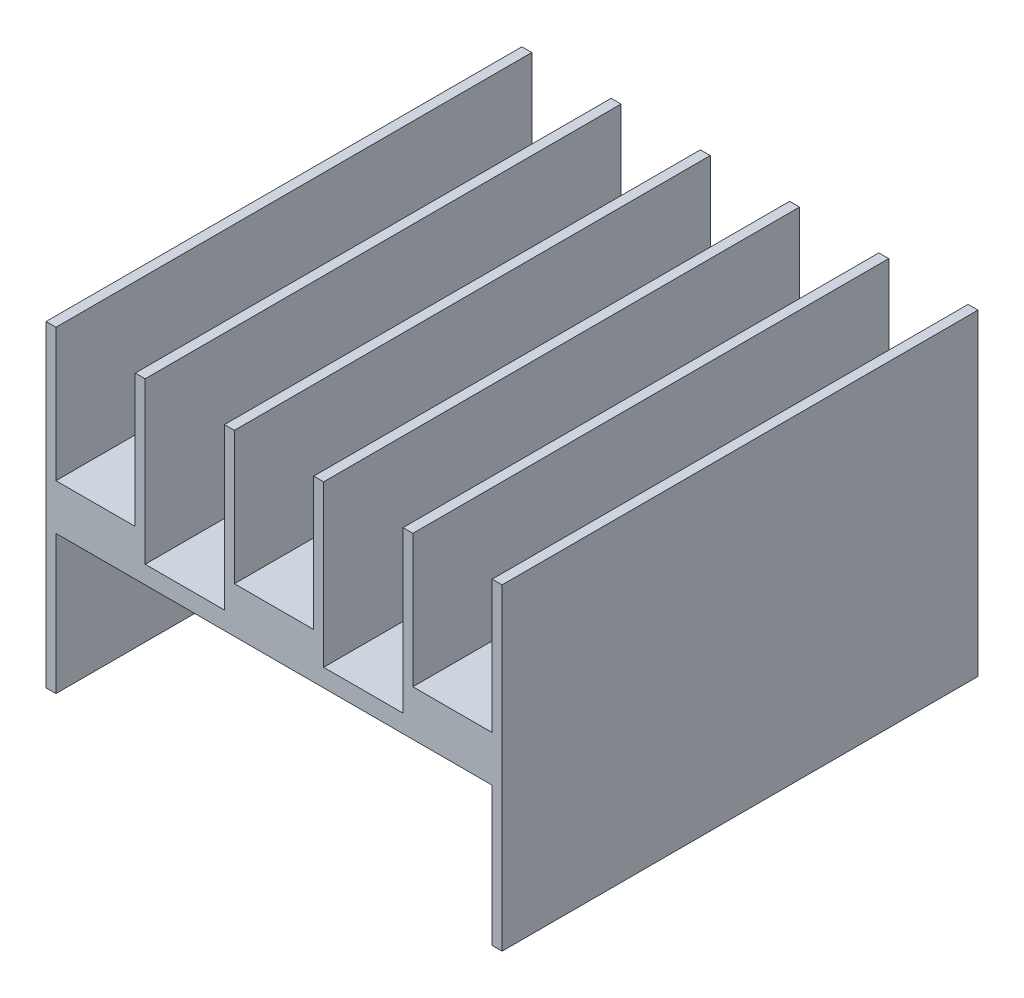
SolidWorks part; units mm, degrees
ref_plane "Front Plane" through (0, 0, 0) normal (0, 0, 1) x (1, 0, 0)
ref_plane "Top Plane" through (0, 0, 0) normal (0, 1, 0) x (1, 0, 0)
ref_plane "Right Plane" through (0, 0, 0) normal (1, 0, 0) x (0, 0, -1)
sketch "Sketch1" plane through (0, 0, 0) normal (0, 0, 1) x (1, 0, 0)
  line L0 (-11, 8) -> (-11, 1.3)
  line L5 (-11.5, 8) -> (-11, 8)
  line L6 (-11.5, 8) -> (-11.5, -8)
  line L7 (-11.5, -8) -> (-11, -8)
  line L8 (11.5, 8) -> (11.5, -8)
  line L9 (-11.5, 8) -> (11.5, -8) construction
  line L11 (-11.5, -8) -> (11.5, 8) construction
  line L12 (-11, 1.3) -> (-7, 1.3)
  line L13 (-7, 1.3) -> (-7, 8)
  line L14 (-6.5, 8) -> (-6.5, -0.1)
  line L15 (-6.5, -0.1) -> (-2.5, -0.1)
  line L16 (-2.5, -0.1) -> (-2.5, 8)
  line L17 (-11, -1) -> (11, -1)
  line L18 (-2, 8) -> (-2, 1.3)
  line L19 (-2, 1.3) -> (2, 1.3)
  line L20 (2, 1.3) -> (2, 8)
  line L21 (2.5, 8) -> (2.5, -0.1)
  line L22 (2.5, -0.1) -> (6.5, -0.1)
  line L23 (6.5, -0.1) -> (6.5, 8)
  line L24 (7, 8) -> (7, 1.3)
  line L25 (7, 1.3) -> (11, 1.3)
  line L26 (11, 1.3) -> (11, 8)
  line L27 (11.5, 8) -> (11.5, -0.1)
  line L28 (-7, 8) -> (-6.5, 8)
  line L29 (-2.5, 8) -> (-2, 8)
  line L30 (15.5, -0.1) -> (15.5, 8) [skipped]
  line L31 (11.5, -0.1) -> (15.5, -0.1) [skipped]
  line L32 (2, 8) -> (2.5, 8)
  line L33 (6.5, 8) -> (7, 8)
  line L34 (11, 8) -> (11.5, 8)
  line L35 (-11, -1) -> (-11, -8)
  line L36 (11, -1) -> (11, -8)
  line L37 (11, -8) -> (11.5, -8)
  point P0 (0, 0)
  dimension "D1" = 3
sketch "Sketch2" plane through (0, 0, 0) normal (0, 0, 1) x (1, 0, 0)
extrude "Boss-Extrude1" add sketch "Sketch1" along normal blind 24 contours L36 L37 L8 L34 L26 L25 L24 L33 L23 L22 L21 L32 L20 L19 L18 L29 L16 L15 L14 L28 L13 L12 L0 L5 L6 L7 L35 L17 region at (0, 0.9183, 0)
sketch "Sketch3" plane through (0, 0, 0) normal (0, 1, 0) x (1, 0, 0)
  circle A0 centre (0, -6) radius 1.5
extrude "Cut-Extrude3" cut sketch "Sketch3" against normal blind 9 and the other way blind 9
thread "Thread1" pitch 0.25 method cut profile "Thread Profile1" start angle 0, offset 0, length 2.3, pitch 0.25, diameter 3
ref_plane "Plane1" through (1.5, -1, 6) normal (0, 0, 1) x (1, 0, 0)
sketch "Thread Profile1" plane through (1.5, -1, 6) normal (0, 0, 1) x (1, 0, 0)
  line L0 (0, 0) -> (0, 0.25) construction
  line L1 (0, 0) -> (0.1353, 0.0781)
  line L2 (0.1353, 0.0781) -> (0.1353, 0.1094)
  line L3 (0.1353, 0.1094) -> (0, 0.1875)
  line L4 (0.1353, 0.0937) -> (0, 0.0937) construction
  line L11 (0, 0) -> (0, 0.1875)
  point P2 (0, 0)
  dimension "Pitch" = 0.25
  dimension "Profile_Angle" = 60
  dimension "Profile_Land" = 0.0312
  dimension "Profile_Height" = 0.1353
